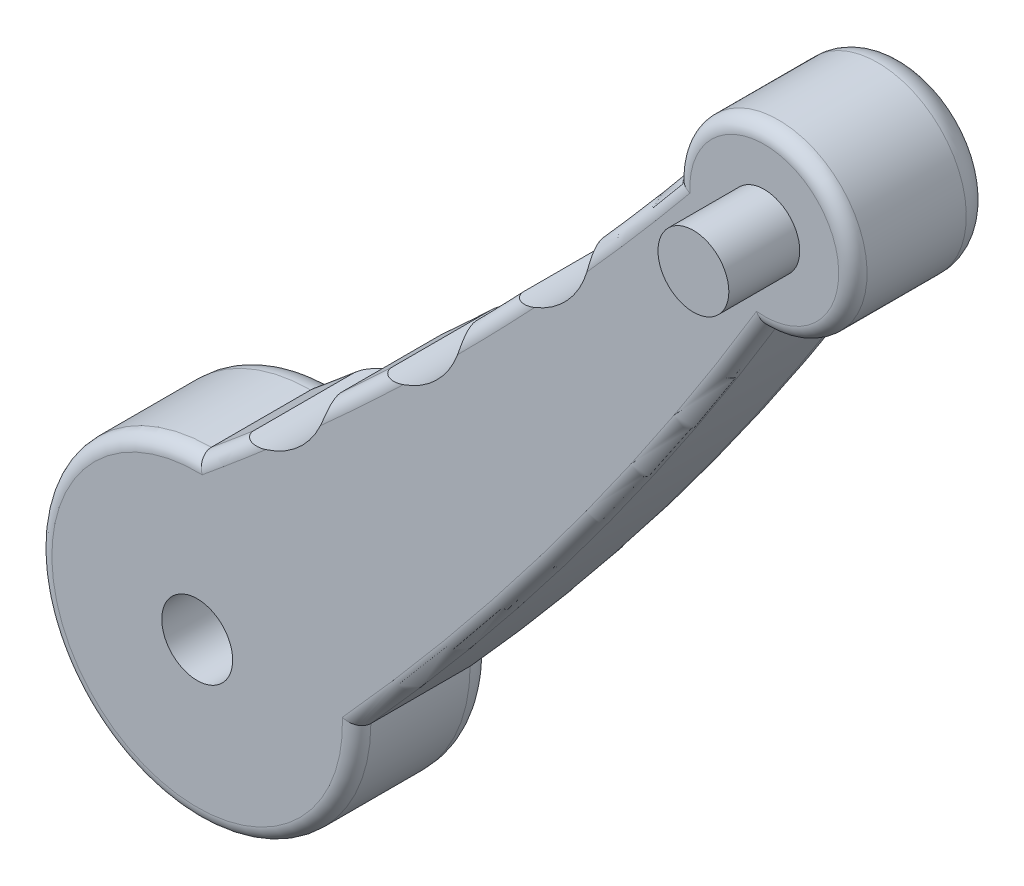
SolidWorks part; units mm, degrees
ref_plane "Front Plane" through (0, 0, 0) normal (0, 0, 1) x (1, 0, 0)
ref_plane "Top Plane" through (0, 0, 0) normal (0, 1, 0) x (1, 0, 0)
ref_plane "Right Plane" through (0, 0, 0) normal (1, 0, 0) x (0, 0, -1)
sketch "Sketch1" plane through (0, 0, 0) normal (0, 0, 1) x (1, 0, 0)
  arc A0 (0, 22.5) -> (22.5, 0) centre (0, 0) ccw
  arc A1 (80, 77.5) -> (67.5, 90) centre (80, 90) ccw
  arc A2 (0, 22.5) -> (67.5, 90) centre (-318.1888, 408.1888) ccw
  arc A3 (22.5, 0) -> (80, 77.5) centre (-348.4249, 335.283) ccw
  dimension "D1" = 45
  dimension "D2" = 25
  dimension "D5" = 500
  dimension "D6" = 500
  dimension "D3" = 90
  dimension "D4" = 80
extrude "Boss-Extrude1" add sketch "Sketch1" along normal mid plane 20 contours A2 A1 A3 A0
fillet "Fillet1" radius 2 4 edges at (35.3646, 54.6354, 10) (88.8388, 98.8388, 10) (53.1241, 37.3595, 10) (-15.9099, -15.9099, 10)
sketch "Sketch2" plane through (0, 0, 10) normal (0, 0, 1) x (1, 0, 0)
  circle A0 centre (0, 0) radius 5
  circle A1 centre (80, 90) radius 5
  dimension "D1" = 10
  dimension "D2" = 10
extrude "Boss-Extrude2" add sketch "Sketch2" along normal blind 10 contours A1
sketch "Sketch4" plane through (0, 0, 10) normal (0, 0, 1) x (1, 0, 0)
  circle A0 centre (0, 0) radius 5
  dimension "D1" = 10
extrude "Cut-Extrude1" cut sketch "Sketch4" against normal blind 10
fillet "Fillet2" radius 4 4 edges at (53.1241, 37.3595, -10) (88.8388, 98.8388, -10) (35.3646, 54.6354, -10) (-15.9099, -15.9099, -10)
sketch "Sketch5" plane through (0, 0, -10) normal (0, 0, -1) x (-1, 0, 0)
  circle A0 centre (0, 0) radius 12.5
  dimension "D1" = 25
extrude "Boss-Extrude3" add sketch "Sketch5" along normal blind 5 contours A0
fillet "Fillet3" radius 5 1 edges at (-12.5, 0, -15)
sketch "Sketch6" plane through (0, 0, -15) normal (0, 0, -1) x (-1, 0, 0)
  line L0 (0, 0) -> (6.6475, 10.5859) construction
  circle A0 centre (6.6475, 10.5859) radius 2.5
  dimension "D2" = 5
  dimension "D1" = 12.5
extrude "Cut-Extrude3" cut sketch "Sketch6" against normal up to surface (5 mm away) contours A0 up to face at (12.5, 0, -10)
pattern_circular "CirPattern1" count 8 over 360 about axis through (0, 0, -15) along (0, 0, -1) of "Cut-Extrude3"
sketch "Sketch7" plane through (0, 0, -10) normal (0, 0, -1) x (-1, 0, 0)
  circle A0 centre (6.6475, 10.5859) radius 1.75
  dimension "D1" = 3.5
extrude "Boss-Extrude4" add sketch "Sketch7" along normal blind 2
fillet "Fillet4" radius 1 1 edges at (-8.3975, 10.5859, -12)
pattern_circular "CirPattern3" count 8 over 360 about axis through (0, 0, -15) along (0, 0, -1) of "Fillet4", "Boss-Extrude4"
sketch "Sketch9" plane through (0, 0, -10) normal (0, 0, -1) x (-1, 0, 0)
  circle A0 centre (-80, 90) radius 5
  arc A6 (-73.9217, 86.7883) -> (-3.2738, 16.1292) centre (318.1888, 408.1888) ccw
  arc A7 (-56.9582, 67.1409) -> (-14.497, 25.6066) centre (318.1888, 408.1888) ccw
  arc A8 (-56.9582, 67.1409) -> (-62.465, 62.8524) centre (-59.548, 64.7865) ccw
  arc A9 (-75.3122, 83.2992) -> (-16.2219, 3.4974) centre (348.4249, 335.283) ccw
  arc A10 (-62.465, 62.8524) -> (-25.8194, 14.3622) centre (348.4249, 335.283) ccw
  arc A11 (-25.8194, 14.3622) -> (-14.497, 25.6066) centre (-19.7465, 19.5698) ccw
  dimension "D3" = 7
  dimension "D4" = 16
  dimension "D5" = 10
  dimension "D1" = 3
  dimension "D2" = 3
extrude "Cut-Extrude4" cut sketch "Sketch9" against normal blind 2 contours A0 | A8 A10 A11 A7
sketch "Sketch11" plane through (0, 0, 0) normal (0, 0, 1) x (1, 0, 0)
  circle A0 centre (43, 76) radius 12.5
  circle A1 centre (25, 57.5) radius 12.5
  circle A2 centre (6, 40) radius 12.5
  point P6 (0, 0)
  point P8 (3.2926, 40)
  point P9 (0, 0)
  dimension "D1" = 25
  dimension "D2" = 76
  dimension "D3" = 57.5
  dimension "D4" = 40
  dimension "D5" = 43
  dimension "D6" = 25
  dimension "D7" = 6
extrude "Cut-Extrude5" cut sketch "Sketch11" against normal mid plane 30
sketch "Sketch12" plane through (0, 0, 10) normal (0, 0, 1) x (1, 0, 0)
  arc A2 (23.3967, 28.1357) -> (35.3038, 39.1848) centre (-318.1888, 408.1888) ccw
  arc A3 (16.0601, 21.6676) -> (67.9047, 73.4459) centre (-318.1888, 408.1888) ccw construction
  arc A5 (28.7444, 22.1858) -> (40.8379, 33.4078) centre (-318.1888, 408.1888) ccw
  arc A6 (33.1094, 26.1541) -> (94.1851, 93.0559) centre (-318.1888, 408.1888) ccw construction
  text T0 "ROBOTIC" font "Century Gothic" height 5
  text T1 "ARM" font "Century Gothic" height 5
  point P0 (33.1094, 26.1541)
  dimension "D1" = 9
  dimension "D2" = 17
sketch "Sketch14" plane through (0, 0, 10) normal (0, 0, 1) x (1, 0, 0)
  arc A2 (28.7444, 22.1858) -> (40.8379, 33.4078) centre (-318.1888, 408.1888) ccw
  arc A3 (37.6727, 30.4011) -> (68.3925, 61.9001) centre (-318.1888, 408.1888) ccw construction
  arc A5 (23.3967, 28.1357) -> (59.2378, 61.9001) centre (-308.6708, 416.5327) ccw construction
  text T0 "ROBOTIC" font "Century Gothic" height 5
  text T1 "ARM" font "Century Gothic" height 5
  point P1 (68.3925, 61.9001)
  point P9 (0, 0)
  point P10 (59.2378, 61.9001)
  point P12 (41.9374, 34.4642)
  point P13 (51.2961, 43.714)
  point P15 (37.6727, 30.4011)
  dimension "D1" = 17
